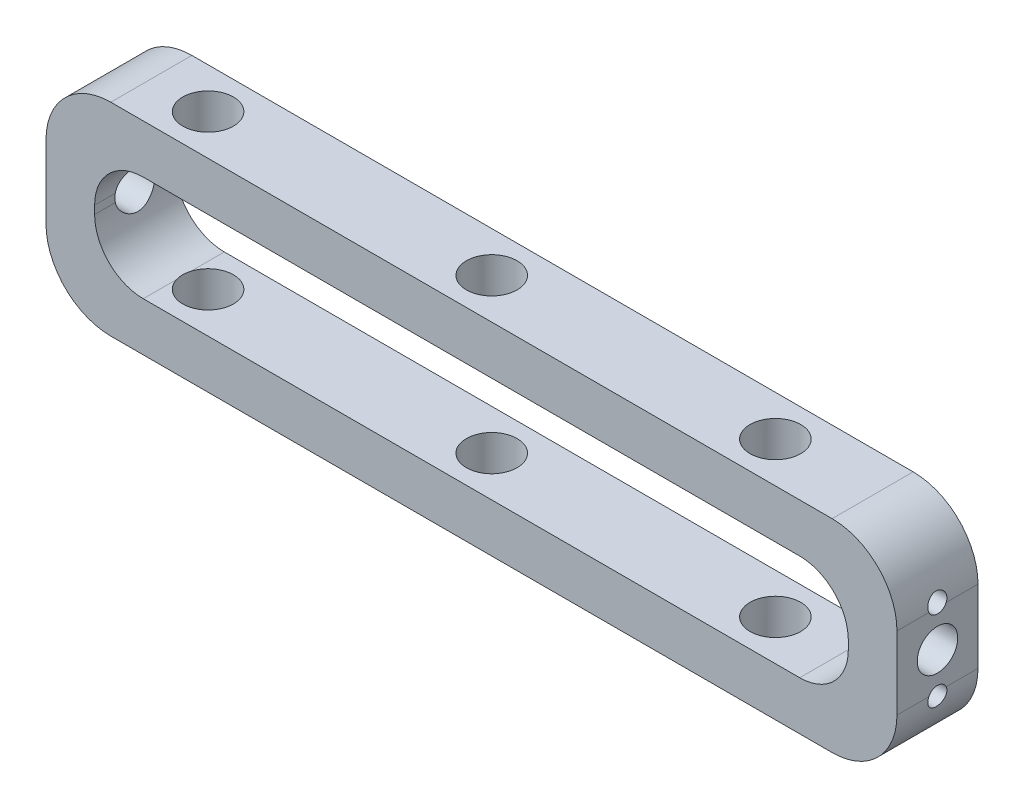
SolidWorks part; units mm, degrees
material "6061 Alloy"
ref_plane "Front Plane" through (0, 0, 0) normal (0, 0, 1) x (1, 0, 0)
ref_plane "Top Plane" through (0, 0, 0) normal (0, 1, 0) x (1, 0, 0)
ref_plane "Right Plane" through (0, 0, 0) normal (1, 0, 0) x (0, 0, -1)
sketch "Sketch1" plane through (0, 0, 0) normal (0, 0, 1) x (1, 0, 0)
  line L0 (59.055, 8.255) -> (-59.055, 8.255)
  line L1 (-59.055, 8.255) -> (-59.055, -8.255)
  line L2 (-66.675, -15.875) -> (-66.675, 15.875)
  line L3 (-66.675, 15.875) -> (66.675, 15.875)
  line L6 (0, 0) -> (-9.6098, 0) construction
  line L7 (0, 0) -> (0, 3.7589) construction
  line L8 (-66.675, -15.875) -> (66.675, -15.875)
  line L9 (59.055, -8.255) -> (-59.055, -8.255)
  line L10 (66.675, -15.875) -> (66.675, 15.875)
  line L11 (59.055, 8.255) -> (59.055, -8.255)
  point P0 (59.055, 0)
  point P3 (-66.675, 0)
  point P21 (-59.055, 0)
  point P22 (0, -8.255)
  point P23 (0, -15.875)
  point P24 (0, 15.875)
  point P25 (0, 8.255)
  point P26 (66.675, 0)
  dimension "D1" = 31.75
  dimension "D2" = 133.35
  dimension "D3" = 7.62
  dimension "D4" = 7.62
extrude "Boss-Extrude1" add sketch "Sketch1" along normal mid plane 12.7 contours L8 L10 L3 L2 L0 L11 L9 L1 | L11 L0 L1 L9
fillet "Fillet2" radius 7.62 4 edges at (59.055, 8.255, 0) (59.055, -8.255, 0) (-59.055, -8.255, 0) (-59.055, 8.255, 0)
sketch "Sketch2" plane through (0, 0, 0) normal (1, 0, 0) x (0, 0, -1)
  circle A0 centre (0, 0) radius 3.175
  dimension "D1" = 6.35
extrude "Cut-Extrude1" cut sketch "Sketch2" against normal through all and the other way through all
sketch "Sketch6" plane through (0, 15.875, 0) normal (0, 1, 0) x (1, 0, 0)
  line L0 (-59.055, 0) -> (59.055, 0) construction
  line L1 (-59.055, -3.175) -> (-59.055, -3.1109) construction
  line L2 (59.055, -6.35) -> (59.055, -3.1109) construction
  line L3 (-66.675, -6.35) -> (-66.675, 6.35) construction
  circle A0 centre (-47.625, 0) radius 11.43
  circle A1 centre (-3.175, 0) radius 11.43
  circle A2 centre (41.275, 0) radius 7.3423
  circle A3 centre (41.275, 0) radius 11.43
  point P18 (0, 0)
  dimension "D1" = 14.6846
  dimension "D2" = 44.45
  dimension "D3" = 44.45
  dimension "D4" = 0
  dimension "D5" = 19.05
hole_wizard "3/8-16 Tapped Hole1" positions "Sketch3" profile "Sketch4" tap size "3/8-16" standard "ANSI Inch" end condition through all
sketch "Sketch3" plane through (0, 15.875, 0) normal (0, 1, 0) x (1, 0, 0)
  point P3 (-47.625, 0)
  point P6 (-3.175, 0)
  point P9 (41.275, 0)
  point P12 (41.275, 0)
sketch "Sketch4" plane through (-47.625, 15.875, 0) normal (1, 0, 0) x (0, 0, 1)
  line L0 (0, 0) -> (0, 31.75)
  line L1 (0, 31.75) -> (3.9687, 31.75)
  line L2 (3.9687, 31.75) -> (3.9687, 0)
  line L5 (3.9687, 0) -> (0, 0)
  line L11 (0, -6.35) -> (0, 107.95) construction
  dimension "Thru Tap Drill Dia." = 7.9375
  dimension "Thru Tap Drill Depth" = 31.75
sketch "Sketch5" plane through (0, 0, 0) normal (1, 0, 0) x (0, 0, -1)
  line L0 (0, -6.35) -> (0, 0) construction
  line L1 (0, 0) -> (2.792, 0) construction
  circle A0 centre (0, -6.35) radius 1.5
  circle A1 centre (0, 6.35) radius 1.5
  dimension "D1" = 3
  dimension "D2" = 12.7
extrude "Cut-Extrude2" cut sketch "Sketch5" along normal through all
fillet "Fillet3" radius 10.16 1 edges at (-66.675, 15.875, 0)
fillet "Fillet4" radius 10.16 1 edges at (-66.675, -15.875, 0)
fillet "Fillet5" radius 10.16 1 edges at (66.675, -15.875, 0)
fillet "Fillet6" radius 10.16 1 edges at (66.675, 15.875, 0)
equation "\"width\" = 6in 'side to side 6"
equation "\"height\"= 1.25in'top to bottom from 1.25"
equation "\"length\"=6.25in 'back to front 6.25"
equation "\"side_width\"= 1in"
equation "\"wheel_di\"=1.875in'2.375"
equation "\"wepon_di\" = 1.25in ' milled rectangle must compensate for bolts ~ - .5 1.5"
equation "\"D1@Sketch1\"=\"wepon_di\""
equation "\"D2@Sketch1\"=\"width\"-.75"
equation "\"wepon_axle\" = 0.1in ' placement from front .5"
equation "\"frame_bolts\" = 0.125"
equation "\"wheel_base\"= 2.5in"
equation "\"cheesing\" = .25in ' width of general trusses"
